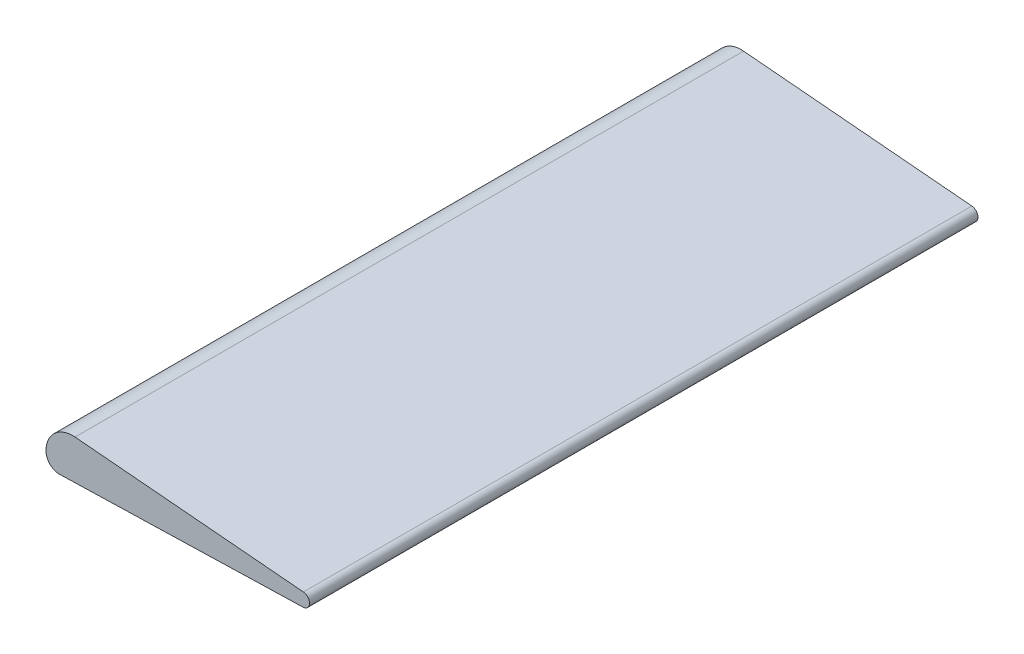
SolidWorks part; units mm, degrees
material "Cast Carbon Steel"
ref_plane "Front Plane" through (0, 0, 0) normal (0, 0, 1) x (1, 0, 0)
ref_plane "Top Plane" through (0, 0, 0) normal (0, 1, 0) x (1, 0, 0)
ref_plane "Right Plane" through (0, 0, 0) normal (1, 0, 0) x (0, 0, -1)
sketch "Sketch1" plane through (0, 0, 0) normal (0, 0, 1) x (1, 0, 0)
  line L0 (0, 0) -> (9.759, 0) construction
  line L1 (1.1046, 1.0121) -> (9.7811, 0.253)
  line L2 (0.5219, -0.5078) -> (9.7659, -0.2539)
  line L3 (0, 0) -> (0, -0.5078) construction
  line L4 (0, -0.5078) -> (0.5219, -0.5078) construction
  arc A0 (1.1046, 1.0121) -> (0, 0) centre (1.016, 0) ccw
  arc A1 (0, 0) -> (0.5219, -0.5078) centre (0.508, 0) ccw
  arc A2 (9.7659, -0.2539) -> (9.7811, 0.253) centre (9.759, 0) ccw
  dimension "D1" = 1.016
  dimension "D2" = 0.508
  dimension "D4" = 0.254
  dimension "D3" = 5
extrude "Boss-Extrude1" add sketch "Sketch1" along normal mid plane 25.4
